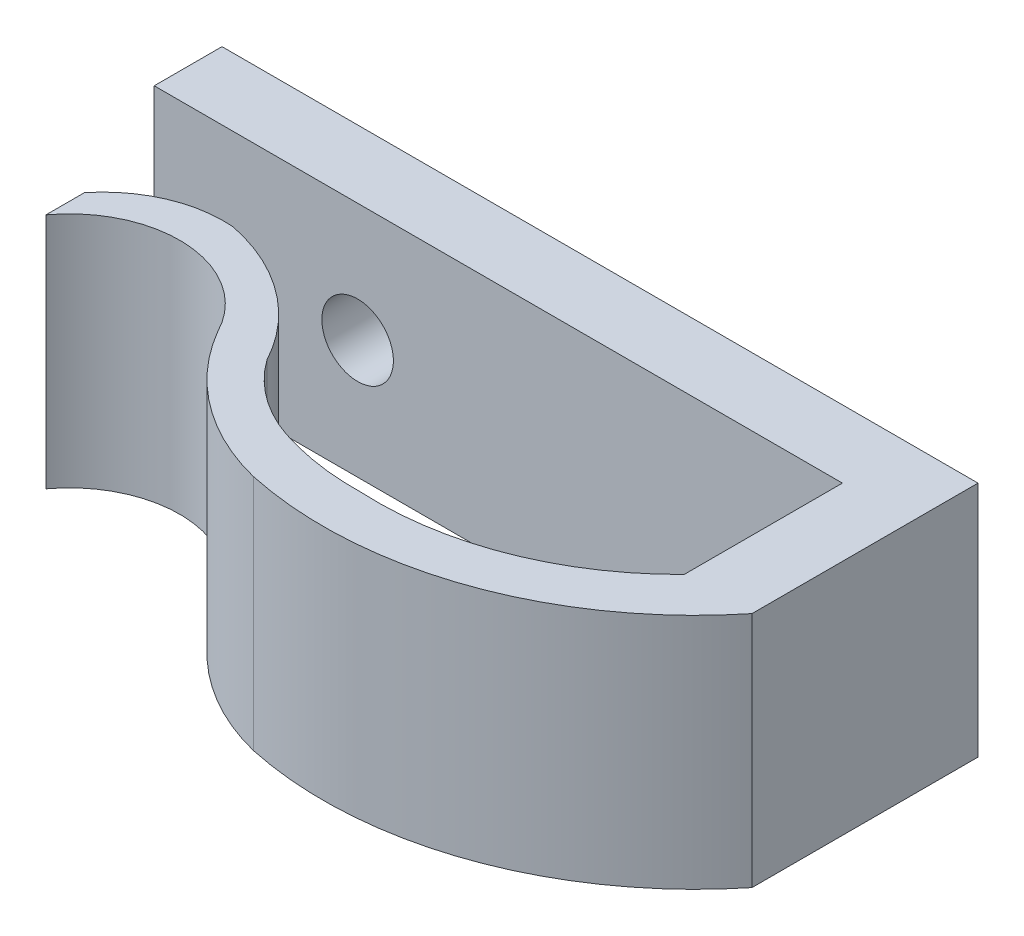
SolidWorks part; units mm, degrees
ref_plane "Front Plane" through (0, 0, 0) normal (0, 0, 1) x (1, 0, 0)
ref_plane "Top Plane" through (0, 0, 0) normal (0, 1, 0) x (1, 0, 0)
ref_plane "Right Plane" through (0, 0, 0) normal (1, 0, 0) x (0, 0, -1)
sketch "Sketch1" plane through (0, 0, 0) normal (0, 0, 1) x (1, 0, 0)
  line L1 (0, 0) -> (33.45, 0)
  line L2 (0, 0) -> (0, 10.5)
  line L3 (0, 10.5) -> (33.45, 10.5)
  line L4 (33.45, 0) -> (33.45, 10.5)
  dimension "D1" = 33.45
  dimension "D2" = 10.5
extrude "Boss-Extrude1" add sketch "Sketch1" along normal blind 3
sketch "Sketch2" plane through (0, 0, 0) normal (0, -1, 0) x (1, 0, 0)
  line L0 (33.45, 3) -> (33.45, 10)
  line L1 (33.45, 3) -> (30.45, 3)
  line L2 (0, 3) -> (33.45, 3) construction
  line L3 (30.45, 3) -> (30.45, 10)
  line L4 (20.1687, 14) -> (24.5808, 14) construction
  line L5 (0, 3) -> (0, 6.6586) construction
  line L6 (0, 6.6586) -> (7.146, 6.6586) construction
  line L7 (2.5511, 8.6392) -> (2.5511, 10.3392)
  arc A0 (20.1687, 14) -> (30.45, 10) centre (20.8749, 0.6021) cw
  arc A1 (7.146, 6.6586) -> (2.5511, 8.6392) centre (6.7223, 11.9959) cw
  arc A2 (17.1673, 15.7789) -> (33.45, 10) centre (20.6221, -0.3152) cw
  arc A3 (7.146, 6.6586) -> (12.9989, 11.0116) centre (5.4552, 15.0433) ccw
  arc A5 (12.9989, 11.0116) -> (16.2592, 13.4247) centre (18.4057, 7.1156) cw
  arc A6 (16.2592, 13.4247) -> (20.1687, 14) centre (19.8885, 2.3318) cw
  arc A8 (2.5511, 10.3392) -> (10.8227, 11.0116) centre (6.4793, 13.2292) ccw
  arc A9 (10.8227, 11.0116) -> (17.1673, 15.7789) centre (19.6517, 5.8671) cw
  dimension "D4" = 1.7
  dimension "D1" = 7
  dimension "D2" = 3
  dimension "D3" = 11
extrude "Boss-Extrude2" add sketch "Sketch2" against normal up to surface (10.5 mm away) up to face at (16.725, 10.5, 1.5)
sketch "Sketch3" plane through (0, 0, 0) normal (0, 0, -1) x (-1, 0, 0)
  line L0 (0, 10.5) -> (0, 0) construction
  circle A0 centre (-9, 5.25) radius 1.5825
  dimension "D1" = 3.165
  dimension "D2" = 9
extrude "Cut-Extrude1" cut sketch "Sketch3" against normal up to next
